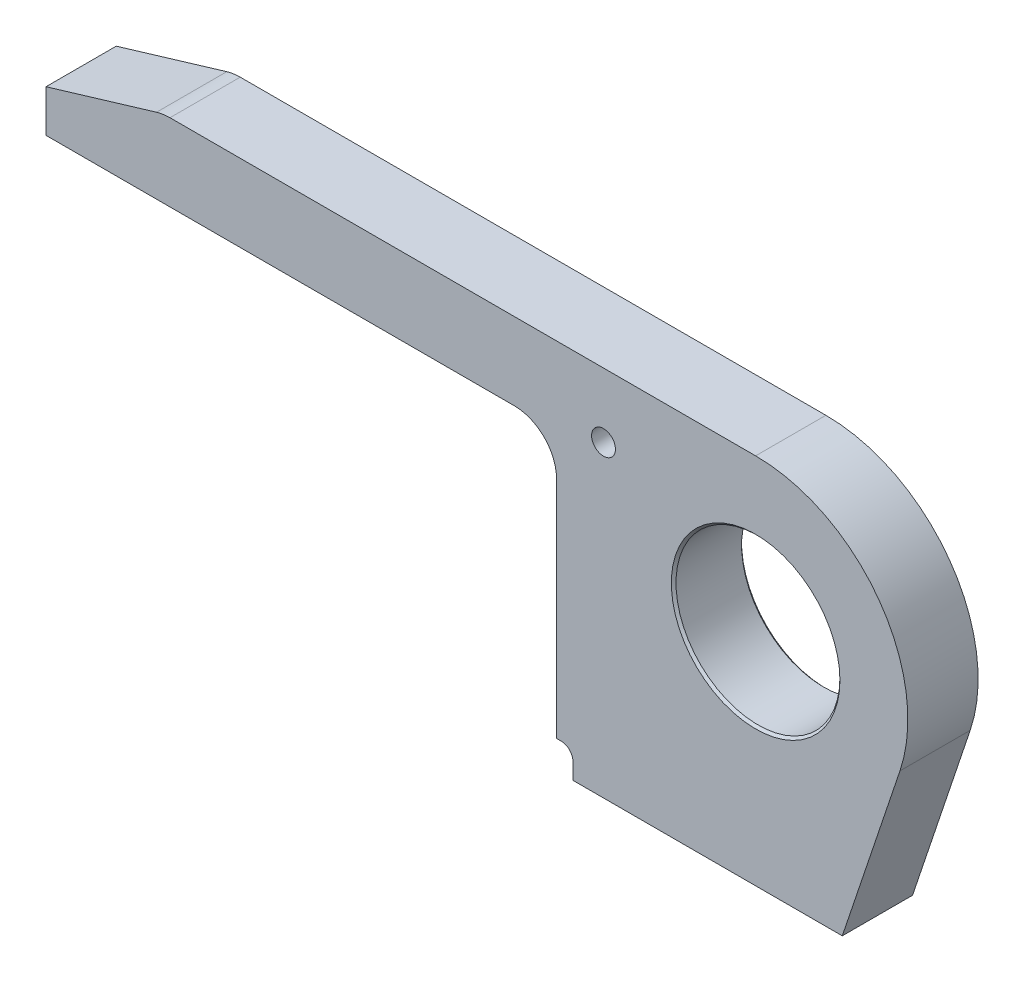
SolidWorks part; units mm, degrees
material "Q355"
ref_plane "前视基准面" through (0, 0, 0) normal (0, 0, 1) x (1, 0, 0)
ref_plane "上视基准面" through (0, 0, 0) normal (0, 1, 0) x (1, 0, 0)
ref_plane "右视基准面" through (0, 0, 0) normal (1, 0, 0) x (0, 0, -1)
sketch "草图1" plane through (0, 0, 0) normal (0, 0, 1) x (1, 0, 0)
  line L0 (-303, 50) -> (-303, 27)
  line L1 (-303, 27) -> (-90, 27)
  line L2 (-90, 27) -> (-90, -82)
  line L3 (-78, -94) -> (37, -94)
  line L5 (0, 65) -> (-253, 65)
  line L6 (37, -94) -> (61.6182, -20.6928)
  line L7 (-90, -82) -> (-78, -82)
  line L8 (-78, -82) -> (-78, -94)
  line L9 (-303, 50) -> (-253, 65)
  circle A0 centre (0, 0) radius 35
  arc A1 (61.6182, -20.6928) -> (0, 65) centre (0, 0) ccw
  dimension "D1" = 70
  dimension "D4" = 130
  dimension "D2" = 94
  dimension "D3" = 115
  dimension "D5" = 303
  dimension "D6" = 213
  dimension "D7" = 38
  dimension "D8" = 12
  dimension "D9" = 12
  dimension "D10" = 15
  dimension "D11" = 50
base flange "基体-法兰1" sketch "草图1" thickness 30 reverse thickness direction no parameters "D1"=2
fillet "圆角1" radius 20 1 edges at (-253, 65, -15)
fillet "圆角2" radius 13 1 edges at (-90, 27, -15)
fillet "圆角3" radius 5 1 edges at (-78, -82, -15)
hole_wizard "M12 螺纹孔1" positions "草图3" profile "草图4" tap size "M12" standard "GB" end condition through all
sketch "草图3" plane through (0, 0, 0) normal (0, 0, 1) x (1, 0, 0)
  line L0 (-64.9519, 37.5) -> (0, 0) construction
  line L4 (0, 65) -> (-250.0646, 65) construction
  point P0 (-64.9519, 37.5)
  dimension "D1" = 75
  dimension "D2" = 30
sketch "草图4" plane through (-64.9519, 37.5, 0) normal (1, 0, 0) x (0, -1, 0)
  line L0 (0, 0) -> (0, 30)
  line L1 (0, 30) -> (5.1, 30)
  line L2 (5.1, 30) -> (5.1, 0)
  line L5 (5.1, 0) -> (0, 0)
  line L11 (0, -6.35) -> (0, 107.95) construction
  dimension "通孔螺纹孔钻头直径" = 10.2
  dimension "通孔螺纹孔钻头深度" = 30
cosmetic thread "孔螺蚊线1"
chamfer "倒角1" distance 5 angle 45 7 edges at (-203, 27, -30) (-203, 27, 0) (-93.8076, 23.1924, -30) (-93.8076, 23.1924, 0) (-90, -34, -30) (-90, -82, -15) (-90, -34, 0)
chamfer "倒角2" distance 1 angle 45 2 edges at (35, 0, -30) (35, 0, 0)
sketch "折弯-线1" [suppressed] plane through (0, 0, 0) normal (0, 1, 0) x (1, 0, 0)
sketch "边界框1" [suppressed] plane through (0, 0, 0) normal (0, 1, 0) x (1, 0, 0)
sheet metal parameters "钣金6" thickness 30 parameters "D1"=2
flat pattern "平板型式6" [suppressed]
sketch "折弯-线2" plane through (0, 0, 0) normal (0, 1, 0) x (1, 0, 0)
sketch3d "边界框2" [suppressed]
  line L0 (-303, -94, 0) -> (65, -94, 0) construction
  line L1 (-303, 65, 0) -> (65, 65, 0) construction
  line L2 (-303, -94, 0) -> (-303, 65, 0) construction
  line L3 (65, -94, 0) -> (65, 65, 0) construction
sheet metal parameters "钣金7" thickness 30 parameters "D1"=2
flat pattern "平板型式6"
sketch "折弯-线2" plane through (0, 0, 0) normal (0, 1, 0) x (1, 0, 0)
sketch3d "边界框2" [suppressed]
  line L0 (-303, -94, 0) -> (65, -94, 0) construction
  line L1 (-303, 65, 0) -> (65, 65, 0) construction
  line L2 (-303, -94, 0) -> (-303, 65, 0) construction
  line L3 (65, -94, 0) -> (65, 65, 0) construction
